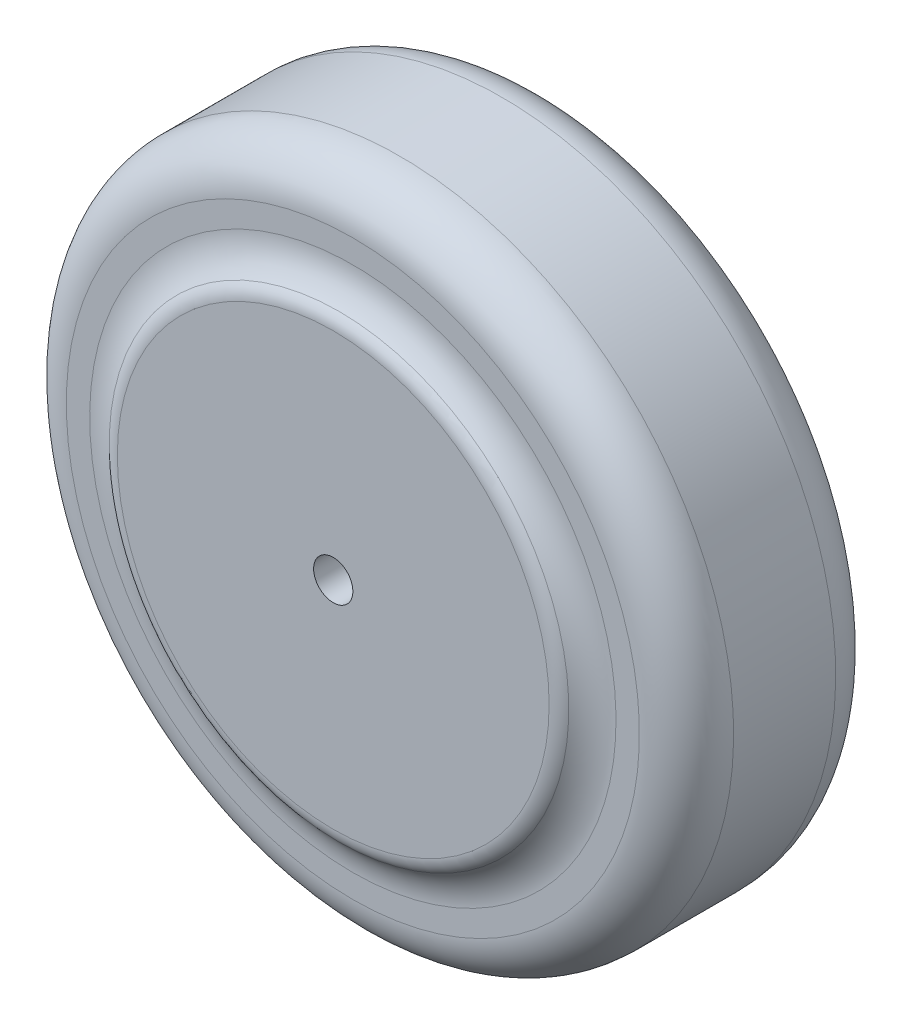
SolidWorks part; units mm, degrees
ref_plane "Front Plane" through (0, 0, 0) normal (0, 0, 1) x (1, 0, 0)
ref_plane "Top Plane" through (0, 0, 0) normal (0, 1, 0) x (1, 0, 0)
ref_plane "Right Plane" through (0, 0, 0) normal (1, 0, 0) x (0, 0, -1)
sketch "Sketch2" plane through (0, 0, 0) normal (0, 1, 0) x (1, 0, 0)
  circle A0 centre (0, 0) radius 85
  dimension "D1" = 170
extrude "Boss-Extrude1" add sketch "Sketch2" along normal blind 50
sketch "Sketch3" plane through (0, 50, 0) normal (0, 1, 0) x (1, 0, 0)
  circle A0 centre (0, 0) radius 60
  dimension "D1" = 120
extrude "Boss-Extrude2" add sketch "Sketch3" along normal blind 5
sketch "Sketch4" plane through (0, 0, 0) normal (0, -1, 0) x (1, 0, 0)
  circle A0 centre (0, 0) radius 60
  dimension "D1" = 120
extrude "Boss-Extrude3" add sketch "Sketch4" along normal blind 5
sketch "Sketch5" plane through (0, 55, 0) normal (0, 1, 0) x (1, 0, 0)
  circle A0 centre (0, 0) radius 5
  dimension "D1" = 10
extrude "Cut-Extrude1" cut sketch "Sketch5" against normal blind 100
sketch "Sketch6" plane through (0, 55, 0) normal (0, 1, 0) x (1, 0, 0)
  point P0 (0, 0)
move or copy body "Body-Move/Copy1" bodies to move or copy 104 copy no rotation origin (0, 10, 0) rotation axis (1, 0, 0) rotation angle 90
fillet "Fillet1" radius 5 2 edges at (0, -50, 45) (0, 70, -15)
fillet "Fillet2" radius 12 3 edges at (0, -75, 40) (0, -50, 40) (0, -75, -10)
